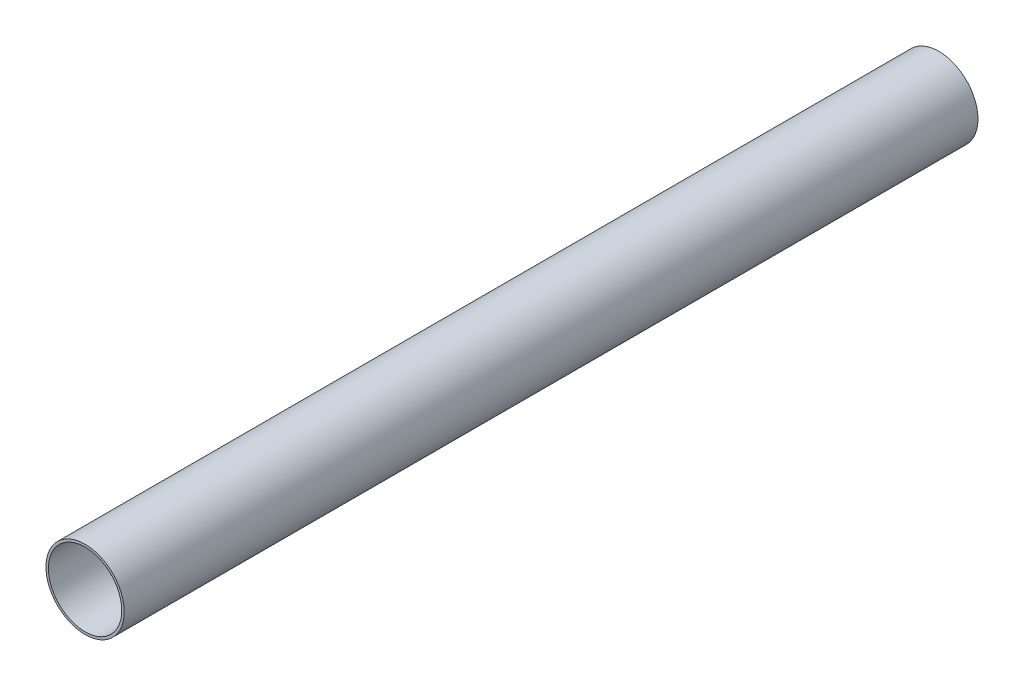
SolidWorks part; units mm, degrees
material "PC High Viscosity"
ref_plane "Front Plane" through (0, 0, 0) normal (0, 0, 1) x (1, 0, 0)
ref_plane "Top Plane" through (0, 0, 0) normal (0, 1, 0) x (1, 0, 0)
ref_plane "Right Plane" through (0, 0, 0) normal (1, 0, 0) x (0, 0, -1)
sketch "Sketch1" plane through (0, 0, 0) normal (0, 0, 1) x (1, 0, 0)
  circle A0 centre (0, 0) radius 23.8125
  circle A1 centre (0, 0) radius 25.4
  dimension "D1" = 50.8
  dimension "D2" = 47.625
extrude "Boss-Extrude1" add sketch "Sketch1" along normal mid plane 554.0375
equation "\"D1@Boss-Extrude1\"=21.125in+3.625mm"
